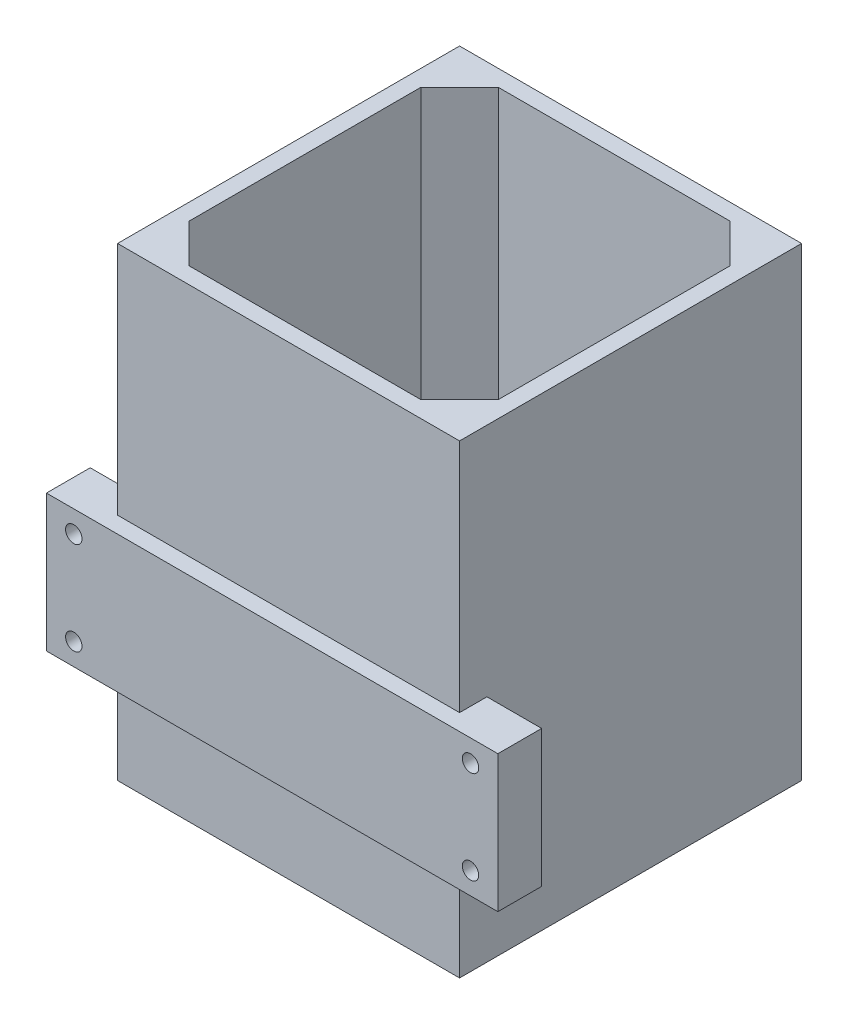
SolidWorks part; units mm, degrees
ref_plane "Front Plane" through (0, 0, 0) normal (0, 0, 1) x (1, 0, 0)
ref_plane "Top Plane" through (0, 0, 0) normal (0, 1, 0) x (1, 0, 0)
ref_plane "Right Plane" through (0, 0, 0) normal (1, 0, 0) x (0, 0, -1)
sketch "Sketch1" plane through (0, 0, 0) normal (0, 1, 0) x (1, 0, 0)
  line L0 (28.25, 21.1789) -> (21.1789, 28.25)
  line L1 (-28.25, -28.25) -> (28.25, -28.25) construction
  line L2 (-28.25, -28.25) -> (-28.25, 28.25) construction
  line L3 (-28.25, 28.25) -> (28.25, 28.25) construction
  line L4 (28.25, -28.25) -> (28.25, 28.25) construction
  line L5 (-28.25, -28.25) -> (28.25, 28.25) construction
  line L6 (-28.25, 28.25) -> (28.25, -28.25) construction
  line L7 (-31.25, -31.25) -> (31.25, -31.25)
  line L8 (-31.25, -31.25) -> (-31.25, 31.25)
  line L9 (-31.25, 31.25) -> (31.25, 31.25)
  line L10 (31.25, -31.25) -> (31.25, 31.25)
  line L11 (-31.25, -31.25) -> (31.25, 31.25) construction
  line L12 (-31.25, 31.25) -> (31.25, -31.25) construction
  line L13 (21.1789, -28.25) -> (28.25, -21.1789)
  line L14 (-21.1789, -28.25) -> (-28.25, -21.1789)
  line L15 (-28.25, 21.1789) -> (-21.1789, 28.25)
  line L16 (-28.25, 21.1789) -> (-28.25, -21.1789)
  line L17 (-21.1789, -28.25) -> (21.1789, -28.25)
  line L18 (28.25, 21.1789) -> (28.25, -21.1789)
  line L19 (-21.1789, 28.25) -> (21.1789, 28.25)
  point P0 (0, 0)
  point P6 (0, 0)
  point P14 (24.7145, 24.7145)
  point P18 (24.7145, -24.7145)
  point P20 (-24.7145, -24.7145)
  point P23 (-24.7145, 24.7145)
  dimension "D1" = 56.5
  dimension "D2" = 56.5
  dimension "D3" = 3
  dimension "D4" = 3
  dimension "D5" = 10
  dimension "D6" = 10
  dimension "D7" = 10
  dimension "D8" = 10
extrude "Boss-Extrude1" add sketch "Sketch1" along normal blind 65
sketch "Sketch3" plane through (0, 0, 0) normal (0, -1, 0) x (1, 0, 0)
  line L1 (-31.25, -31.25) -> (31.25, -31.25)
  line L2 (-31.25, -31.25) -> (-31.25, 31.25)
  line L3 (-31.25, 31.25) -> (31.25, 31.25)
  line L4 (31.25, -31.25) -> (31.25, 31.25)
  circle A0 centre (0, 0) radius 22.5
  dimension "D1" = 45
extrude "Boss-Extrude3" add sketch "Sketch3" along normal blind 20
fillet "Fillet1" radius 10 6 edges at (-28.25, 0, 0) (0, 0, 28.25) (-24.7145, 0, 24.7145) (28.25, 0, 0) (0, 0, -28.25) (-24.7145, 0, -24.7145)
sketch "Sketch4" plane through (0, 0, 31.25) normal (0, 0, 1) x (1, 0, 0)
  line L1 (-41.25, -3) -> (41.25, -3)
  line L2 (-41.25, -3) -> (-41.25, 22)
  line L3 (-41.25, 22) -> (41.25, 22)
  line L4 (41.25, -3) -> (41.25, 22)
  line L6 (31.25, 65) -> (31.25, -20) construction
  line L7 (-31.25, 65) -> (-31.25, -20) construction
  line L8 (13.1601, 0) -> (-13.1601, 0) construction
  circle A0 centre (36.25, 18) radius 1.5
  circle A1 centre (36.25, 1) radius 1.5
  circle A2 centre (-36.25, 1) radius 1.5
  circle A3 centre (-36.25, 18) radius 1.5
  dimension "D5" = 3
  dimension "D10" = 3
  dimension "D11" = 3
  dimension "D12" = 4
  dimension "D13" = 5
  dimension "D14" = 5
  dimension "D1" = 25
  dimension "D2" = 10
  dimension "D3" = 10
  dimension "D4" = 3
  dimension "D6" = 4
  dimension "D7" = 4
  dimension "D8" = 5
  dimension "D9" = 5
extrude "Boss-Extrude4" add sketch "Sketch4" along normal blind 3
sketch "Sketch6" plane through (0, 0, 31.25) normal (0, 0, -1) x (-1, 0, 0)
  line L0 (31.25, 22) -> (31.25, -3) construction
  line L1 (-41.25, 22) -> (-31.25, 22)
  line L2 (-41.25, 22) -> (-41.25, -3)
  line L3 (-41.25, -3) -> (-31.25, -3)
  line L4 (-31.25, 22) -> (-31.25, -3)
  line L5 (31.25, 22) -> (41.25, 22)
  line L6 (31.25, 22) -> (31.25, -3)
  line L7 (31.25, -3) -> (41.25, -3)
  line L8 (41.25, 22) -> (41.25, -3)
  line L9 (31.25, 22) -> (41.25, 22) construction
  circle A0 centre (-36.25, 18) radius 1.5
  circle A1 centre (-36.25, 1) radius 1.5
  circle A2 centre (36.25, 18) radius 1.5
  circle A3 centre (36.25, 1) radius 1.5
  dimension "D1" = 0
extrude "Boss-Extrude5" add sketch "Sketch6" along normal blind 5
